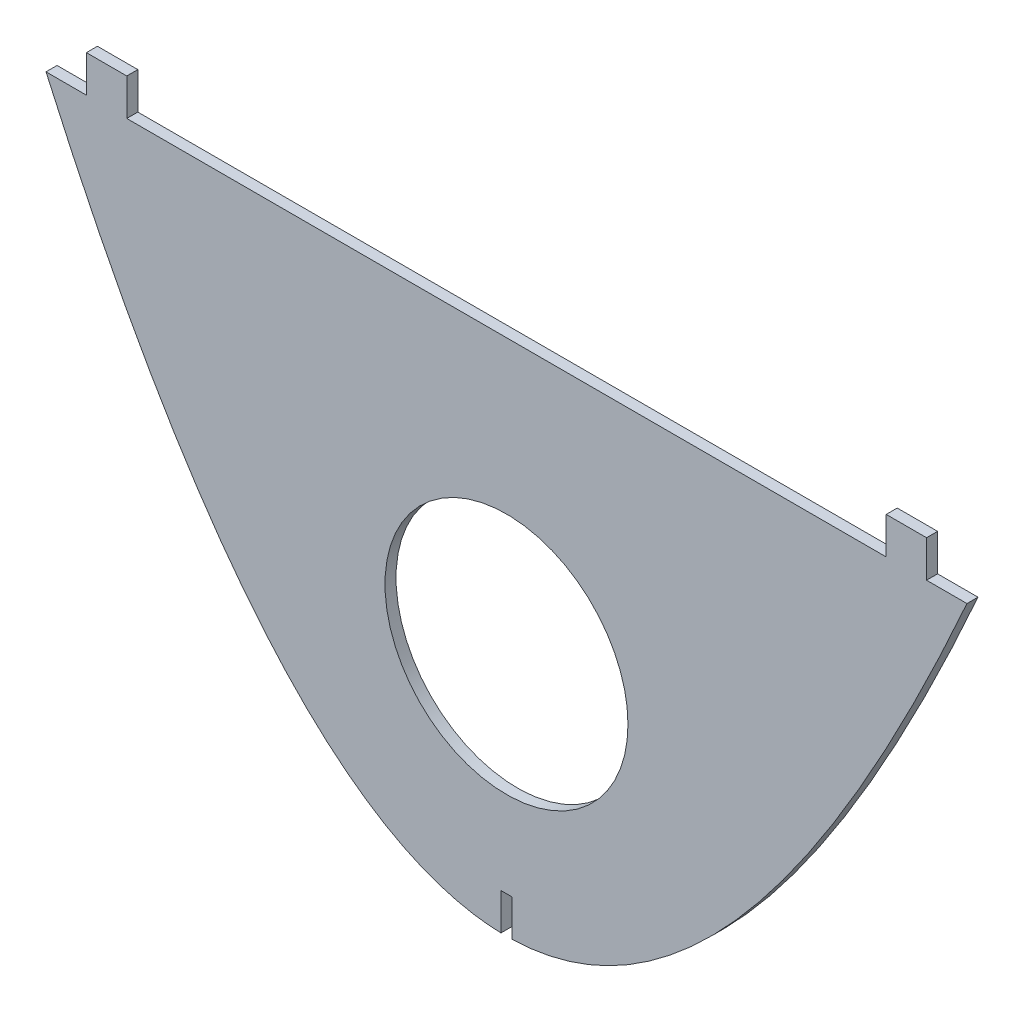
SolidWorks part; units mm, degrees
ref_plane "Front Plane" through (0, 0, 0) normal (0, 0, 1) x (1, 0, 0)
ref_plane "Top Plane" through (0, 0, 0) normal (0, 1, 0) x (1, 0, 0)
ref_plane "Right Plane" through (0, 0, 0) normal (1, 0, 0) x (0, 0, -1)
sketch "Sketch1" plane through (0, 0, 0) normal (0, 0, 1) x (1, 0, 0)
  line L2 (-125.0778, 140.8) -> (-114.1082, 140.8)
  line L3 (125.0778, 140.8) -> (114.1082, 140.8)
  line L4 (-114.1082, 140.8) -> (-114.1082, 150.8)
  line L5 (-114.1082, 150.8) -> (-103.1387, 150.8)
  line L6 (-103.1387, 150.8) -> (-103.1387, 140.8)
  line L7 (114.1082, 140.8) -> (114.1082, 150.8)
  line L8 (114.1082, 150.8) -> (103.1387, 150.8)
  line L9 (103.1387, 150.8) -> (103.1387, 140.8)
  line L10 (-103.1387, 140.8) -> (103.1387, 140.8)
  spline S0 degree 2 poles (-140.3417, 177.2623) (0, -177.2623) (140.3417, 177.2623) knots 0 0 0 1 1 1 construction
  spline S1 degree 2 poles (-125.0778, 140.8) (0, -140.8) (125.0778, 140.8) knots 0.054382 0.054382 0.054382 0.945618 0.945618 0.945618
extrude "Boss-Extrude1" add sketch "Sketch1" along normal blind 3
sketch "Sketch2" plane through (0, 0, 0) normal (0, 0, 1) x (1, 0, 0)
  line L4 (-1.5, 10) -> (1.5, 10)
  line L5 (-1.5, 10) -> (-1.5, -4.3244)
  line L6 (-1.5, -4.3244) -> (1.5, -4.3244)
  line L7 (1.5, 10) -> (1.5, -4.3244)
extrude "Cut-Extrude1" cut sketch "Sketch2" along normal blind 13
sketch "Sketch3" plane through (0, 0, 0) normal (0, 0, 1) x (1, 0, 0)
  circle A0 centre (0, 66.3355) radius 33
  dimension "D1" = 66
extrude "Cut-Extrude2" cut sketch "Sketch3" along normal through all
